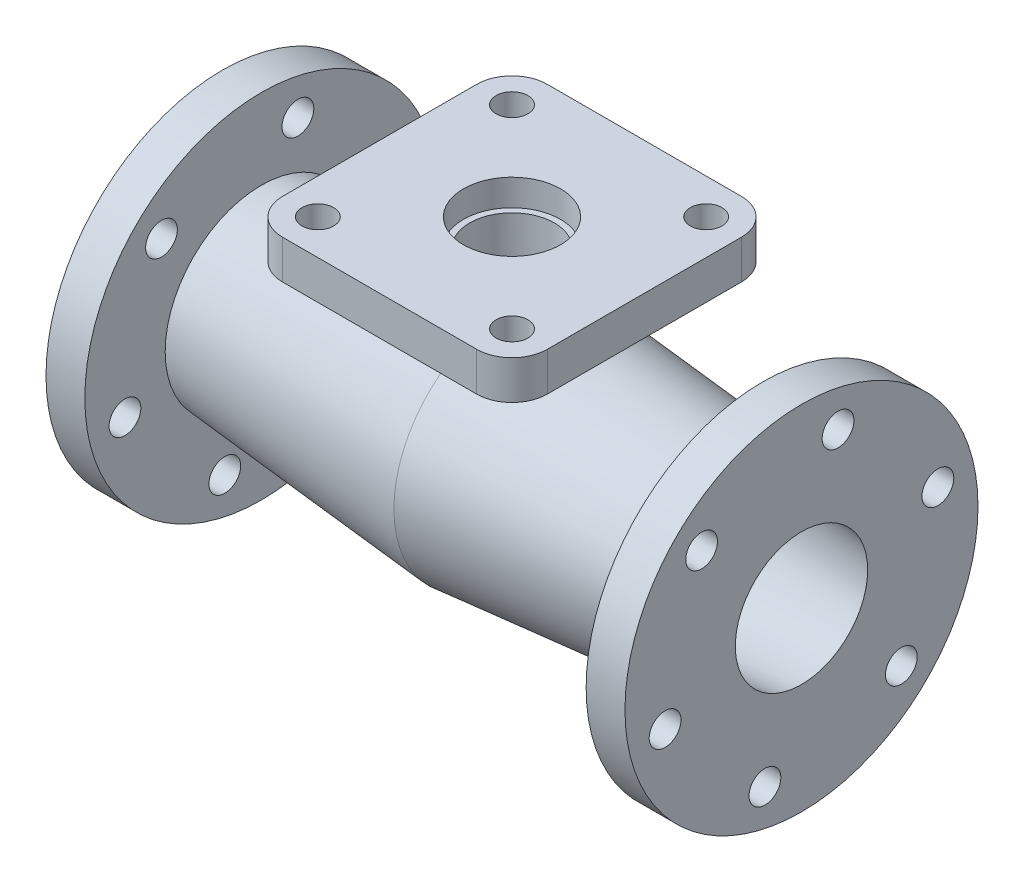
SolidWorks part; units mm, degrees
ref_plane "Front Plane" through (0, 0, 0) normal (0, 0, 1) x (1, 0, 0)
ref_plane "Top Plane" through (0, 0, 0) normal (0, 1, 0) x (1, 0, 0)
ref_plane "Right Plane" through (0, 0, 0) normal (1, 0, 0) x (0, 0, -1)
sketch "Sketch1" plane through (0, 0, 0) normal (0, 0, 1) x (1, 0, 0)
  line L0 (0, 0) -> (-393516.8918, 0) construction
  line L1 (0, 9.8117) -> (0, -393507.0802) construction
  line L2 (-164, -37.5) -> (-164, -100)
  line L3 (-164, -100) -> (-142, -100)
  line L4 (-142, -100) -> (-142, -54.482)
  line L5 (-142, -54.482) -> (0, -66.9054)
  line L6 (-164, -37.5) -> (0, -51.8481)
  line L7 (164, -37.5) -> (0, -51.8481)
  line L8 (164, -37.5) -> (164, -100)
  line L9 (164, -100) -> (142, -100)
  line L10 (142, -100) -> (142, -54.482)
  line L11 (142, -54.482) -> (0, -66.9054)
  dimension "D1" = 22
  dimension "D2" = 284
  dimension "D3" = 328
  dimension "D4" = 75
  dimension "D5" = 15
  dimension "D6" = 5
  dimension "D7" = 200
revolve "Revolve1" add sketch "Sketch1" angle 360 about L0
ref_plane "Plane1" through (0, 110, 0) normal (0, 1, 0) x (1, 0, 0)
sketch "Sketch2" plane through (0, 110, 0) normal (0, 1, 0) x (1, 0, 0)
  line L1 (-55, 75) -> (55, 75)
  line L2 (-75, 55) -> (-75, -55)
  line L3 (-55, -75) -> (55, -75)
  line L4 (75, 55) -> (75, -55)
  line L5 (0, -75) -> (0, 75) construction
  line L6 (-75, 0) -> (75, 0) construction
  arc A0 (-75, -55) -> (-55, -75) centre (-55, -55) ccw
  arc A1 (55, -75) -> (75, -55) centre (55, -55) ccw
  arc A2 (55, 75) -> (75, 55) centre (55, 55) cw
  arc A3 (-55, 75) -> (-75, 55) centre (-55, 55) ccw
  circle A4 centre (-55, 55) radius 9
  circle A5 centre (55, 55) radius 9
  circle A6 centre (-55, -55) radius 9
  circle A7 centre (55, -55) radius 9
  circle A8 centre (0, 0) radius 24
  circle A9 centre (0, 0) radius 27.5
  circle A10 centre (0, 0) radius 40
  point P0 (0, 0)
  point P6 (-75, -75)
  point P12 (75, -75)
  point P17 (-75, 75)
  dimension "D3" = 20
  dimension "D4" = 18
  dimension "D5" = 48
  dimension "D6" = 55
  dimension "D7" = 80
  dimension "D1" = 150
  dimension "D2" = 150
extrude "Boss-Extrude1" add sketch "Sketch2" against normal blind 22 separate body contours L1 A3 L2 A0 L3 A1 L4 A2 A10 A7 A6 A5 A4 region at (0, 110, -72.8787)
sketch "Sketch3" plane through (164, 0, 0) normal (1, 0, 0) x (0, 0, -1)
  line L0 (0, 0) -> (-50000, 0) construction
  line L1 (0, 0) -> (0, -50000) construction
  line L2 (0, 0) -> (-77.2741, -20.7055) construction
  line L3 (0, 0) -> (-77.2741, -20.7055) construction
  circle A0 centre (-77.2741, -20.7055) radius 9
  circle A1 centre (0, 0) radius 80 construction
  circle A2 centre (-56.5685, 56.5685) radius 9
  circle A3 centre (20.7055, 77.2741) radius 9
  circle A4 centre (77.2741, 20.7055) radius 9
  circle A5 centre (56.5685, -56.5685) radius 9
  circle A6 centre (-20.7055, -77.2741) radius 9
  point P10 (0, 0)
  dimension "D1" = 160
  dimension "D3" = 18
  dimension "D2" = 15
  dimension "D5" = 80
  dimension "D4" = 6
extrude "Boss-Extrude6" add sketch "Sketch2<8>" against normal up to next contours A10 A9 | A9 A8 | A8 region at (0, 110, 0) region at (-26.7222, 110, 0) region at (-38.8686, 110, 0)
sketch "Sketch2<8>" plane through (0, 110, 0) normal (0, 1, 0) x (1, 0, 0) same geometry as "Sketch2"
sketch "Sketch7" plane through (0, 0, 0) normal (0, 0, 1) x (1, 0, 0)
  line L0 (0, 19.4004) -> (0, 110)
  line L1 (-55, 110) -> (55, 110) construction
  line L2 (0, 110) -> (27.5, 110)
  line L3 (27.5, 110) -> (27.5, 95)
  line L4 (27.5, 95) -> (24, 95)
  line L5 (24, 95) -> (22.6804, 19.4004)
  line L6 (22.6804, 19.4004) -> (0, 19.4004)
  line L7 (0, 0) -> (-50000, 0) construction
  line L8 (0, 0) -> (0, -50000) construction
  dimension "D1" = 55
  dimension "D2" = 15
  dimension "D3" = 48
  dimension "D4" = 1
revolve "Cut-Revolve1" cut sketch "Sketch7" angle 360 about L8
sketch "Sketch8" plane through (164, 0, 0) normal (1, 0, 0) x (0, 0, -1)
  line L0 (0, 0) -> (-50000, 0) construction
  line L1 (0, 0) -> (0, -50000) construction
  line L2 (0, 0) -> (-77.2741, -20.7055) construction
  line L3 (0, 0) -> (-77.2741, -20.7055) construction
  circle A0 centre (0, 0) radius 80 construction
  circle A1 centre (-77.2741, -20.7055) radius 9
  circle A2 centre (-56.5685, 56.5685) radius 9
  circle A3 centre (20.7055, 77.2741) radius 9
  circle A4 centre (77.2741, 20.7055) radius 9
  circle A5 centre (56.5685, -56.5685) radius 9
  circle A6 centre (-20.7055, -77.2741) radius 9
  point P9 (0, 0)
  dimension "D1" = 160
  dimension "D2" = 18
  dimension "D3" = 15
  dimension "D5" = 80
  dimension "D4" = 6
extrude "Cut-Extrude5" cut sketch "Sketch8" against normal up to next
mirror "Mirror1" about plane through (0, 0, 0) normal (1, 0, 0) of "Cut-Extrude5"
